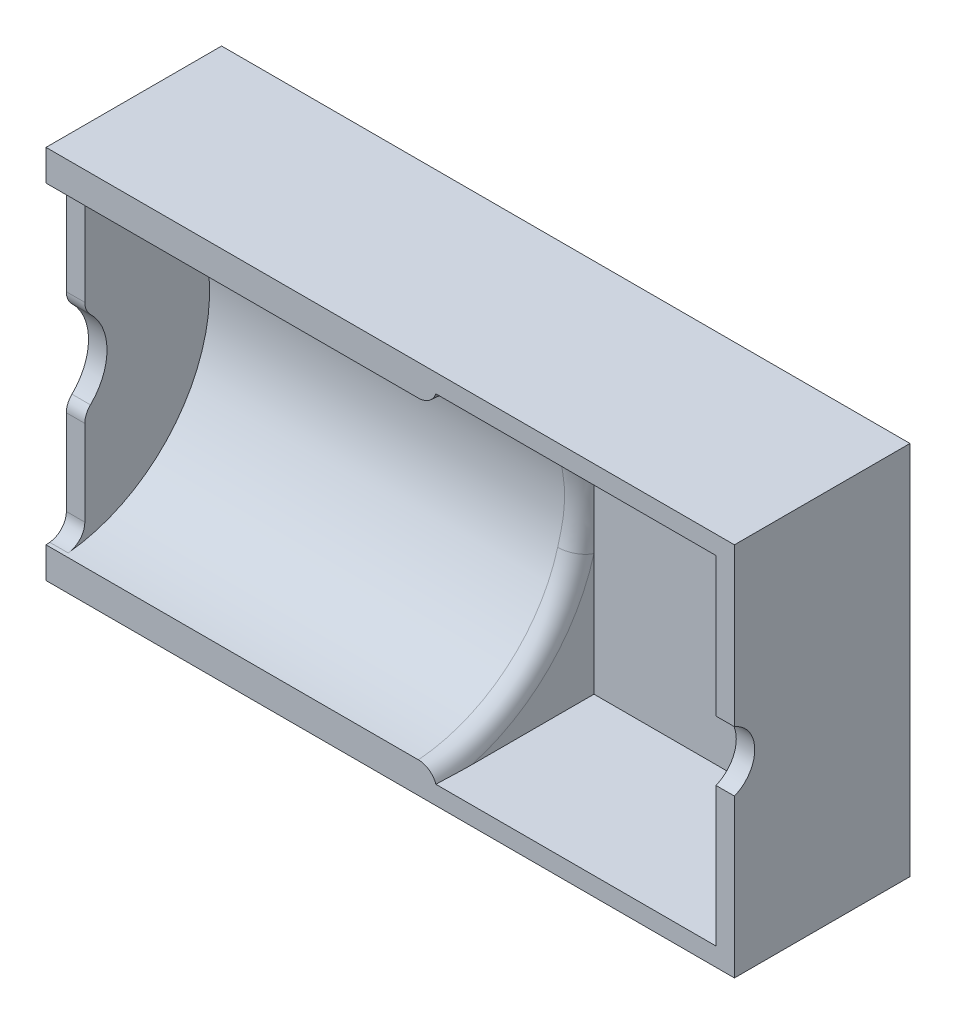
SolidWorks part; units mm, degrees
material "6063-T5"
ref_plane "Front Plane" through (0, 0, 0) normal (1, 0, 0) x (0, 1, 0)
ref_plane "Top Plane" through (0, 0, 0) normal (0, 0, 1) x (0, 1, 0)
ref_plane "Right Plane" through (0, 0, 0) normal (0, 1, 0) x (-1, 0, 0)
ref_plane "Plane1" through (-27.75, 0, 0) normal (1, 0, 0) x (0, 1, 0)
ref_plane "Plane2" through (-66.5, 0, 0) normal (1, 0, 0) x (0, 1, 0)
sketch "Sketch1" plane through (0, 0, 0) normal (1, 0, 0) x (0, 1, 0)
  line L0 (-18.3, -1.3) -> (-18.3, -18.3)
  line L1 (-16.3, -16.3) -> (16.3, -16.3) construction
  line L2 (-16.3, -16.3) -> (-16.3, 16.3) construction
  line L3 (-16.3, 16.3) -> (16.3, 16.3) construction
  line L4 (16.3, -16.3) -> (16.3, 16.3) construction
  line L5 (-16.3, -16.3) -> (16.3, 16.3) construction
  line L6 (-16.3, 16.3) -> (16.3, -16.3) construction
  line L7 (-18.3, -18.3) -> (18.3, -18.3)
  line L8 (18.3, -18.3) -> (18.3, -1.3)
  line L9 (18.3, -1.3) -> (20.3, -1.3)
  line L10 (20.3, -1.3) -> (20.3, -20.3)
  line L11 (20.3, -20.3) -> (-20.3, -20.3)
  line L12 (-20.3, -20.3) -> (-20.3, -1.3)
  line L13 (-20.3, -1.3) -> (-18.3, -1.3)
  line L14 (-16.3, -16.3) -> (-18.3, -16.3) construction
  line L15 (16.3, -16.3) -> (18.3, -16.3) construction
  line L16 (0, -16.3) -> (0, -18.3) construction
  line L17 (-18.3, -18.3) -> (-20.3, -18.3) construction
  line L18 (18.3, -18.3) -> (20.3, -18.3) construction
  line L19 (0, -18.3) -> (0, -20.3) construction
  point P0 (0, 0)
  dimension "D1" = 32.6
  dimension "D2" = 32.6
  dimension "D3" = 2
  dimension "D4" = 2
  dimension "D5" = 15
extrude "Boss-Extrude1" add sketch "Sketch1" against normal blind 28.2 and the other way blind 2
sketch "Sketch2" plane through (-28.2, 0, 0) normal (-1, 0, 0) x (0, -1, 0)
  line L8 (-18.3, -1.3) -> (-16.9502, -1.3)
  line L9 (18.3, -1.3) -> (16.9502, -1.3)
  line L16 (20.3, -1.3) -> (18.3, -1.3)
  line L17 (18.3, -1.3) -> (18.3, -18.3)
  line L18 (18.3, -18.3) -> (-18.3, -18.3)
  line L19 (-18.3, -18.3) -> (-18.3, -1.3)
  line L20 (-18.3, -1.3) -> (-20.3, -1.3)
  line L21 (-20.3, -1.3) -> (-20.3, -20.3)
  line L22 (-20.3, -20.3) -> (20.3, -20.3)
  line L23 (20.3, -20.3) -> (20.3, -1.3)
  line L24 (20.3, -1.3) -> (18.3, -1.3)
  line L28 (-18.3, -1.3) -> (-20.3, -1.3)
  line L29 (-20.3, -1.3) -> (-20.3, -20.3)
  line L30 (-20.3, -20.3) -> (20.3, -20.3)
  line L31 (20.3, -20.3) -> (20.3, -1.3)
  circle A0 centre (0, 0) radius 15 construction
  arc A1 (-16.9502, -1.3) -> (16.9502, -1.3) centre (0, 0) ccw
  circle A2 centre (0, 0) radius 16.05 construction
  dimension "D2" = 30
  dimension "D3" = 2
  dimension "D4" = 32.1
  dimension "D1" = 0
extrude "Boss-Extrude2" add sketch "Sketch2" along normal offset from surface (40.3 mm away) 2 up to plane "Plane2" offset beyond the face yes
sketch "Sketch3" plane through (2, 0, 0) normal (1, 0, 0) x (0, 1, 0)
  line L0 (3.2496, -1.3) -> (20.3, -1.3)
  line L1 (-20.3, -1.3) -> (-3.2496, -1.3)
  line L2 (-20.3, -1.3) -> (-20.3, -20.3)
  line L3 (-20.3, -20.3) -> (20.3, -20.3)
  line L4 (20.3, -1.3) -> (20.3, -20.3)
  arc A0 (-3.2496, -1.3) -> (3.2496, -1.3) centre (0, 0) ccw
  dimension "D1" = 7
extrude "Boss-Extrude3" add sketch "Sketch3" along normal blind 2
sketch "Sketch4" plane through (-68.5, 0, 0) normal (-1, 0, 0) x (0, -1, 0)
  line L2 (-20.3, -1.3) -> (-20.3, -20.3)
  line L3 (-20.3, -20.3) -> (20.3, -20.3)
  line L4 (20.3, -1.3) -> (20.3, -20.3)
  line L5 (20.3, -1.3) -> (20.3, -20.3) construction
  line L10 (16.9502, -1.3) -> (20.3, -1.3)
  line L11 (-20.3, -1.3) -> (-16.9502, -1.3)
  line L12 (-4.7497, -3.5) -> (-16.6358, -3.5)
  line L13 (4.7497, -3.5) -> (16.6358, -3.5)
  arc A0 (-4.7497, -3.5) -> (4.7497, -3.5) centre (0, 0) ccw
  arc A1 (-16.9502, -1.3) -> (-16.6358, -3.5) centre (0, 0) ccw
  arc A2 (-16.9502, -1.3) -> (16.9502, -1.3) centre (0, 0) ccw construction
  arc A3 (16.6358, -3.5) -> (16.9502, -1.3) centre (0, 0) ccw
  dimension "D1" = 11.8
  dimension "D2" = 3.5
extrude "Boss-Extrude4" add sketch "Sketch4" along normal blind 2
fillet "Fillet1" radius 2 1 edges at (-28.2, 0, -17)
fillet "Fillet2" radius 2 4 edges at (-69.5, 4.7497, -3.5) (-69.5, -4.7497, -3.5) (-69.5, -16.6358, -3.5) (-69.5, 16.6358, -3.5)
